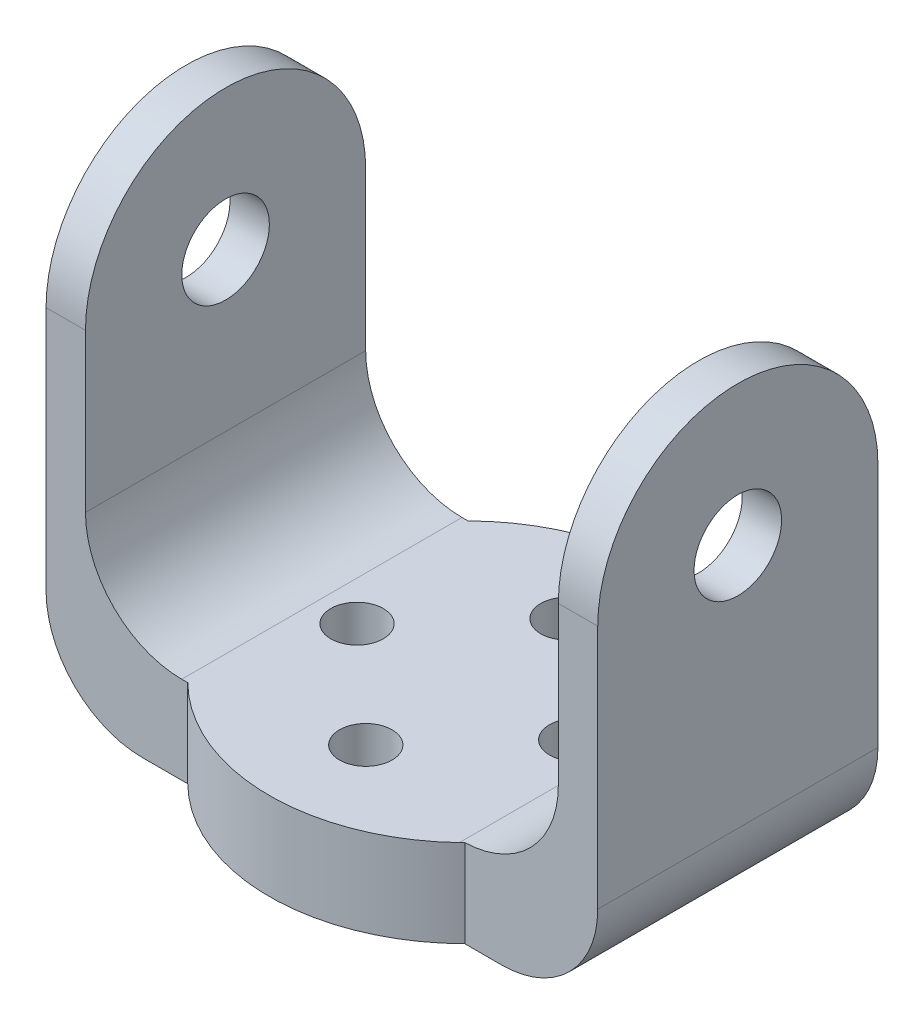
SolidWorks part; units mm, degrees
ref_plane "Front Plane" through (0, 0, 0) normal (0, 0, 1) x (1, 0, 0)
ref_plane "Top Plane" through (0, 0, 0) normal (0, 1, 0) x (1, 0, 0)
ref_plane "Right Plane" through (0, 0, 0) normal (1, 0, 0) x (0, 0, -1)
sketch "Sketch1" plane through (0, 0, 0) normal (0, 0, 1) x (1, 0, 0)
  line L0 (-19.1129, 28.1855) -> (-19.1129, -26.8145)
  line L1 (-19.1129, -26.8145) -> (43.8871, -26.8145)
  line L2 (43.8871, -26.8145) -> (43.8871, 28.1855)
  line L3 (43.8871, 28.1855) -> (39.3871, 28.1855)
  line L4 (39.3871, 28.1855) -> (39.3871, -16.8145)
  line L5 (39.3871, -16.8145) -> (-14.6129, -16.8145)
  line L6 (-14.6129, -16.8145) -> (-14.6129, 28.1855)
  line L7 (-14.6129, 28.1855) -> (-19.1129, 28.1855)
  point P10 (-3.7903, 7.8629)
  dimension "D1" = 4.5
  dimension "D2" = 4.5
  dimension "D3" = 54
  dimension "D4" = 55
  dimension "D5" = 45
  dimension "D6" = 55
extrude "Boss-Extrude1" add sketch "Sketch1" along normal blind 32
sketch "Sketch2" plane through (0, -26.8145, 0) normal (0, -1, 0) x (1, 0, 0)
  line L0 (-19.1129, 0) -> (43.8871, 0) construction
  line L2 (-19.1129, 32) -> (-19.1129, 0) construction
  circle A0 centre (12.8871, 16) radius 22.5
  dimension "D1" = 45
  dimension "D2" = 16
  dimension "D3" = 32
extrude "Boss-Extrude4" add sketch "Sketch2" against normal blind 10
sketch "Sketch3" plane through (43.8871, 0, 0) normal (1, 0, 0) x (0, 0, -1)
  line L0 (6.5, -16.8145) -> (0, -16.8145) construction
  line L2 (-32, -26.8145) -> (-32, 28.1855) construction
  circle A0 centre (-16, 12.1855) radius 5
  dimension "D1" = 10
  dimension "D2" = 29
  dimension "D3" = 16
extrude "Cut-Extrude1" cut sketch "Sketch3" against normal through all both and the other way through all
fillet "Fillet3" radius 11 4 edges at (43.8871, -26.8145, 16) (-19.1129, -26.8145, 16) (39.3871, -16.8145, 16) (-14.6129, -16.8145, 16)
fillet "Fillet4" 2 edges at (41.6371, 28.1855, 32) (41.6371, 28.1855, 0) type full round first side face at (37.3367, -5.7346, 32) second side face at (37.3367, -5.7346, 0) middle face at (41.6371, 28.1855, 16)
fillet "Fillet5" 2 edges at (-16.8629, 28.1855, 32) (-16.8629, 28.1855, 0) type full round first side face at (-11.1998, -7.1341, 32) second side face at (-11.1998, -7.1341, 0) middle face at (-16.8629, 28.1855, 16)
sketch "Sketch4" plane through (0, -16.8145, 0) normal (0, 1, 0) x (1, 0, 0)
  line L0 (-3.6129, 0) -> (-3.6129, -32) construction
  circle A0 centre (12.3871, -4.0104) radius 3
  circle A1 centre (24.8767, -15.5) radius 3
  arc A2 (28.3871, 0.3095) -> (-2.9322, 0) centre (12.8871, -16) ccw construction
  circle A3 centre (13.3871, -27.9896) radius 3
  circle A4 centre (0.8975, -16.5) radius 3
  point P7 (12.8871, -16)
  dimension "D1" = 6
  dimension "D2" = 12
  dimension "D3" = 16
  dimension "D4" = 4
extrude "Cut-Extrude2" cut sketch "Sketch4" against normal through all both and the other way through all
